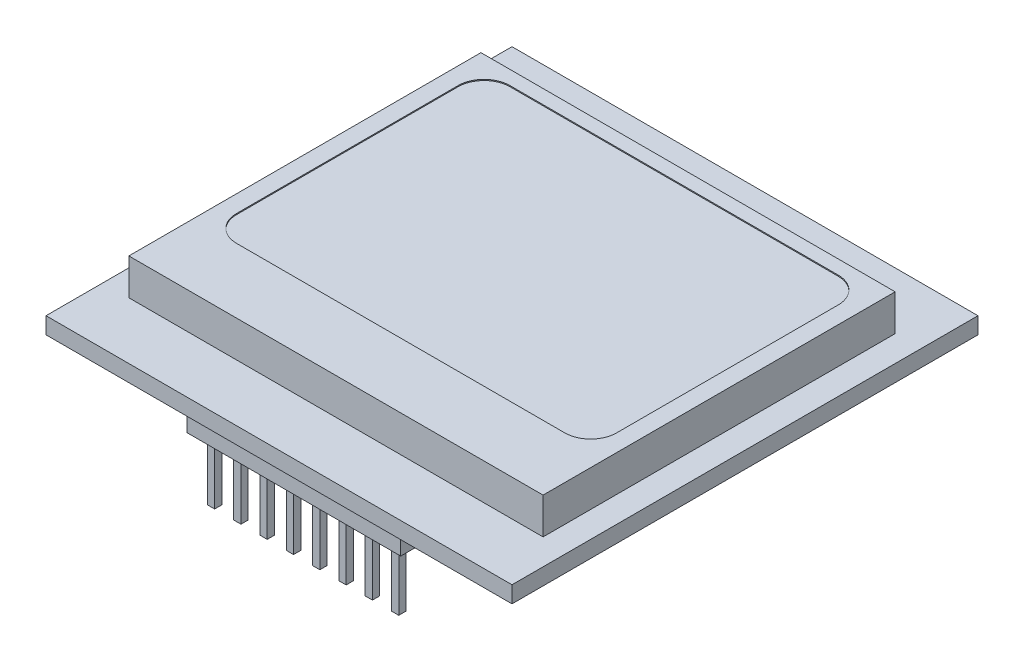
SolidWorks part; units mm, degrees
ref_plane "Front Plane" through (0, 0, 0) normal (0, 0, 1) x (1, 0, 0)
ref_plane "Top Plane" through (0, 0, 0) normal (0, 1, 0) x (1, 0, 0)
ref_plane "Right Plane" through (0, 0, 0) normal (1, 0, 0) x (0, 0, -1)
sketch "Sketch1" plane through (0, 0, 0) normal (0, 1, 0) x (1, 0, 0)
  line L1 (-22.5, 22.5) -> (22.5, 22.5)
  line L2 (-22.5, 22.5) -> (-22.5, -22.5)
  line L3 (-22.5, -22.5) -> (22.5, -22.5)
  line L4 (22.5, 22.5) -> (22.5, -22.5)
  line L5 (-22.5, 22.5) -> (22.5, -22.5) construction
  line L6 (-22.5, -22.5) -> (22.5, 22.5) construction
  point P0 (0, 0)
  dimension "D1" = 45
  dimension "D2" = 45
extrude "Boss-Extrude1" add sketch "Sketch1" along normal blind 1.6
sketch "Sketch2" plane through (0, 1.6, 0) normal (0, 1, 0) x (1, 0, 0)
  line L1 (-20, 17) -> (20, 17)
  line L2 (-20, 17) -> (-20, -17)
  line L3 (-20, -17) -> (20, -17)
  line L4 (20, 17) -> (20, -17)
  line L5 (-20, 17) -> (20, -17) construction
  line L6 (-20, -17) -> (20, 17) construction
  point P0 (0, 0)
  dimension "D1" = 40
  dimension "D2" = 34
extrude "Boss-Extrude2" add sketch "Sketch2" along normal blind 3.5
sketch "Sketch4" plane through (0, 0, 0) normal (0, -1, 0) x (1, 0, 0)
  line L0 (0, 22.5) -> (0, -22.5) construction
  line L1 (-22.5, 22.5) -> (22.5, 22.5) construction
  line L2 (22.5, -22.5) -> (-22.5, -22.5) construction
  line L3 (0, 21.075) -> (0, 18.575) construction
  line L4 (-10.33, 21.075) -> (10.33, 21.075)
  line L5 (-10.33, 21.075) -> (-10.33, 18.575)
  line L6 (-10.33, 18.575) -> (10.33, 18.575)
  line L7 (10.33, 21.075) -> (10.33, 18.575)
  line L8 (-10.33, 19.825) -> (10.33, 19.825) construction
  line L9 (-22.5, 0) -> (22.5, 0) construction
  line L10 (-22.5, -22.5) -> (-22.5, 22.5) construction
  line L11 (22.5, 22.5) -> (22.5, -22.5) construction
  dimension "D1" = 20.66
  dimension "D2" = 2.5
  dimension "D3" = 19.825
extrude "Boss-Extrude3" add sketch "Sketch4" along normal blind 2.8
sketch "Sketch5" plane through (0, -2.8, 0) normal (0, -1, 0) x (1, 0, 0)
  line L0 (-10.33, 19.825) -> (10.33, 19.825) construction
  line L1 (0, 21.075) -> (0, 18.575) construction
  line L2 (1.62, 20.175) -> (1.62, 19.475)
  line L3 (-1.62, 20.175) -> (-0.92, 20.175)
  line L4 (-10.33, 21.075) -> (-10.33, 18.575)
  line L5 (-10.33, 18.575) -> (10.33, 18.575)
  line L6 (10.33, 18.575) -> (10.33, 21.075)
  line L7 (10.33, 21.075) -> (-10.33, 21.075)
  line L8 (-10.33, 21.075) -> (-10.33, 18.575)
  line L9 (-10.33, 18.575) -> (10.33, 18.575)
  line L10 (10.33, 18.575) -> (10.33, 21.075)
  line L11 (10.33, 21.075) -> (-10.33, 21.075)
  line L12 (-1.62, 20.175) -> (-1.62, 19.475)
  line L13 (-1.62, 19.475) -> (-0.92, 19.475)
  line L14 (-0.92, 20.175) -> (-0.92, 19.475)
  line L15 (-1.62, 20.175) -> (-0.92, 19.475) construction
  line L16 (-1.62, 19.475) -> (-0.92, 20.175) construction
  line L17 (0.92, 19.475) -> (1.62, 19.475)
  line L18 (0.92, 20.175) -> (0.92, 19.475)
  line L19 (0.92, 20.175) -> (1.62, 20.175)
  line L20 (4.16, 20.175) -> (4.16, 19.475)
  line L21 (3.46, 19.475) -> (4.16, 19.475)
  line L22 (3.46, 20.175) -> (3.46, 19.475)
  line L23 (3.46, 20.175) -> (4.16, 20.175)
  line L24 (6.7, 20.175) -> (6.7, 19.475)
  line L25 (6, 19.475) -> (6.7, 19.475)
  line L26 (6, 20.175) -> (6, 19.475)
  line L27 (6, 20.175) -> (6.7, 20.175)
  line L28 (9.24, 20.175) -> (9.24, 19.475)
  line L29 (8.54, 19.475) -> (9.24, 19.475)
  line L30 (8.54, 20.175) -> (8.54, 19.475)
  line L31 (8.54, 20.175) -> (9.24, 20.175)
  line L32 (-3.46, 20.175) -> (-3.46, 19.475)
  line L33 (-4.16, 19.475) -> (-3.46, 19.475)
  line L34 (-4.16, 20.175) -> (-4.16, 19.475)
  line L35 (-4.16, 20.175) -> (-3.46, 20.175)
  line L36 (-6, 20.175) -> (-6, 19.475)
  line L37 (-6.7, 19.475) -> (-6, 19.475)
  line L38 (-6.7, 20.175) -> (-6.7, 19.475)
  line L39 (-6.7, 20.175) -> (-6, 20.175)
  line L40 (-8.54, 20.175) -> (-8.54, 19.475)
  line L41 (-9.24, 19.475) -> (-8.54, 19.475)
  line L42 (-9.24, 20.175) -> (-9.24, 19.475)
  line L43 (-9.24, 20.175) -> (-8.54, 20.175)
  point P8 (-1.27, 19.825)
  dimension "D2" = 0.7
  dimension "D3" = 0.7
  dimension "D4" = 2.54
  dimension "D1" = 0
  dimension "D5" = 5
  dimension "D6" = 4
extrude "Boss-Extrude4" add sketch "Sketch5" along normal blind 5.95 contours L43 L42 L41 L40 | L39 L38 L37 L36 | L35 L34 L33 L32 | L14 L3 L12 L13 | L19 L18 L17 L2 | L23 L22 L21 L20 | L27 L26 L25 L24 | L31 L30 L29 L28 region at (1.27, -2.8, 19.825) region at (-1.27, -2.8, 19.825) region at (3.81, -2.8, 19.825) region at (6.35, -2.8, 19.825) region at (8.89, -2.8, 19.825) region at (-3.81, -2.8, 19.825) region at (-6.35, -2.8, 19.825) region at (-8.89, -2.8, 19.825)
sketch "Sketch6" plane through (0, 5.1, 0) normal (0, 1, 0) x (1, 0, 0)
  line L0 (0, 17) -> (0, -17) construction
  line L1 (20, 17) -> (-20, 17) construction
  line L2 (-20, -17) -> (20, -17) construction
  line L4 (-15.85, 15.65) -> (15.85, 15.65)
  line L5 (-18.35, 13.15) -> (-18.35, -8.25)
  line L6 (-15.85, -10.75) -> (15.85, -10.75)
  line L7 (18.35, 13.15) -> (18.35, -8.25)
  line L8 (-18.35, 15.65) -> (18.35, -10.75) construction
  line L9 (-18.35, -10.75) -> (18.35, 15.65) construction
  arc A0 (-18.35, -8.25) -> (-15.85, -10.75) centre (-15.85, -8.25) ccw
  arc A1 (15.85, -10.75) -> (18.35, -8.25) centre (15.85, -8.25) ccw
  arc A2 (15.85, 15.65) -> (18.35, 13.15) centre (15.85, 13.15) cw
  arc A3 (-15.85, 15.65) -> (-18.35, 13.15) centre (-15.85, 13.15) ccw
  point P6 (0, 2.45)
  dimension "D4" = 2.5
  dimension "D1" = 36.7
  dimension "D2" = 26.4
  dimension "D3" = 1.35
extrude "Cut-Extrude1" cut sketch "Sketch6" against normal blind 0.1
mirror "Mirror1" about plane through (0, 0, 0) normal (0, 0, 1) of "Boss-Extrude4", "Boss-Extrude3"
equation "\"D3@Sketch4\"=39.65/2"
